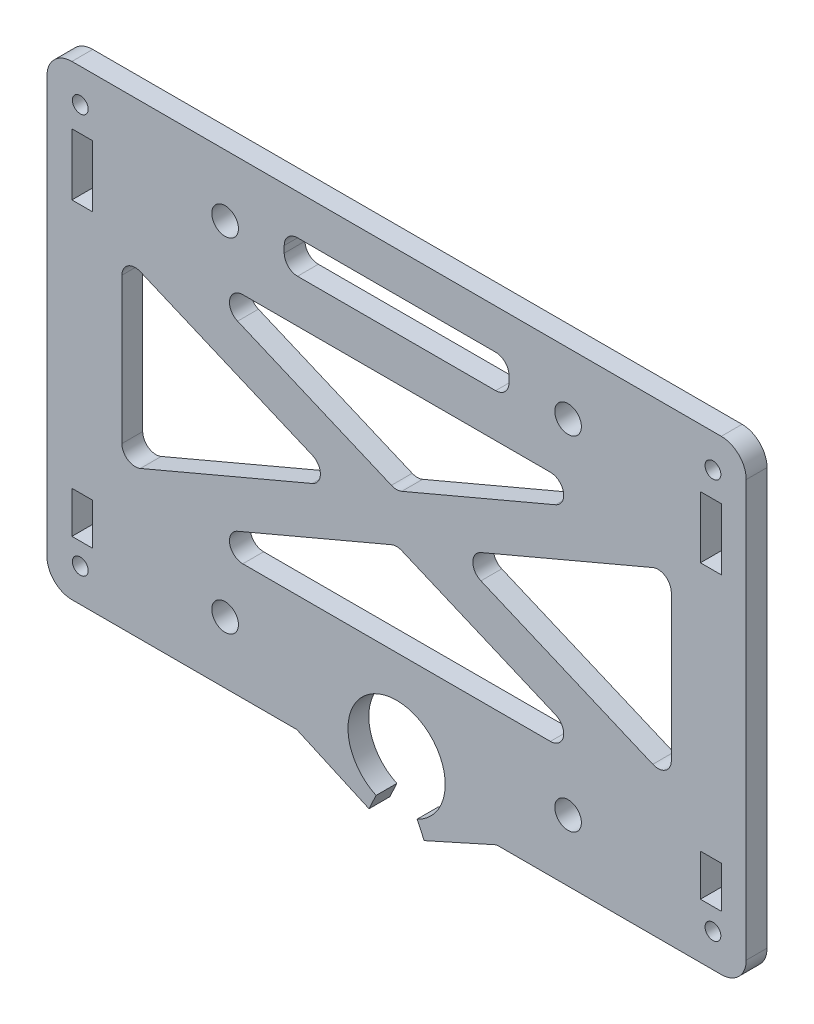
SolidWorks part; units mm, degrees
material "Delrin 2700 NC010, Low Viscosity Acetal Copolymer (SS)"
ref_plane "Front Plane" through (0, 0, 0) normal (0, 0, 1) x (1, 0, 0)
ref_plane "Top Plane" through (0, 0, 0) normal (0, 1, 0) x (1, 0, 0)
ref_plane "Right Plane" through (0, 0, 0) normal (1, 0, 0) x (0, 0, -1)
sketch "Sketch1" plane through (0, 0, 0) normal (0, 0, 1) x (1, 0, 0)
  line L0 (0, -1000) -> (0, 49000) construction
  line L1 (24.765, 17.78) -> (-24.765, 17.78)
  line L2 (26.67, 15.875) -> (26.67, -17.78)
  line L3 (26.67, -17.78) -> (-26.67, -17.78)
  line L4 (-26.67, 15.875) -> (-26.67, -17.78)
  line L5 (26.67, 17.78) -> (-26.67, -17.78) construction
  line L6 (26.67, -17.78) -> (-26.67, 17.78) construction
  line L7 (-1000, 0) -> (49000, 0) construction
  line L8 (-7.62, -17.78) -> (-2.104, -20.26)
  line L15 (-2.104, -20.26) -> (0, -15.748)
  line L16 (7.62, -17.78) -> (2.104, -20.26)
  line L17 (2.104, -20.26) -> (0, -15.748)
  line L18 (0, 0) -> (-24.2469, 20.3456) construction
  circle A0 centre (0, -15.748) radius 3.7084
  circle A1 centre (-24.13, 15.24) radius 0.6032
  circle A2 centre (-13.08, -13.08) radius 1.016
  circle A3 centre (24.13, 15.24) radius 0.6033
  circle A4 centre (-13.08, 13.08) radius 1.016
  circle A5 centre (13.08, 13.08) radius 1.016
  circle A6 centre (13.08, -13.08) radius 1.016
  arc A7 (24.765, -17.78) -> (26.67, -15.875) centre (24.765, -15.875) ccw
  arc A8 (-24.765, -17.78) -> (-26.67, -15.875) centre (-24.765, -15.875) cw
  arc A9 (-24.765, 17.78) -> (-26.67, 15.875) centre (-24.765, 15.875) ccw
  arc A10 (24.765, 17.78) -> (26.67, 15.875) centre (24.765, 15.875) cw
  circle A11 centre (24.13, -15.24) radius 0.6033
  circle A12 centre (-24.13, -15.24) radius 0.6032
  circle A13 centre (0, -15.748) radius 4.9784
  point P0 (0, 0)
  point P9 (0, 0)
  point P11 (0, -7.366)
  point P53 (-13.97, 0)
  dimension "D6" = 7.4168
  dimension "D7" = 1.2065
  dimension "D9" = 2.032
  dimension "D14" = 1.905
  dimension "D15" = 1.905
  dimension "D30" = 2.54
  dimension "D1" = 35.56
  dimension "D4" = 53.34
  dimension "D5" = 15.748
  dimension "D8" = 2.54
  dimension "D10" = 13.08
  dimension "D11" = 13.08
  dimension "D19" = 40
  dimension "D20" = 8.382
  dimension "D21" = 4
  dimension "D23" = 13.97
  dimension "D27" = 7.62
  dimension "D28" = 25
  dimension "D26" = 1.27
extrude "Boss-Extrude1" add sketch "Sketch1" along normal blind 1.5875 contours A10 L1 A9 L4 L3 A0 L2 A6 A5 A4 A1 A2 A3 | L3 A13 L15 A0 | A13 L3 L8 | L3 A13 A0 | L17 A13 L3 A0 | A13 L16 L3 region at (0, 0.4732, 0) region at (5.0756, -18.4873, 0) region at (-5.0756, -18.4873, 0) region at (2.9865, -18.87, 0) region at (3.8235, -17.6582, 0) region at (-2.9865, -18.87, 0)
ref_axis "Axis1" through (0, 0, 0) along (0, 0, 1)
sketch "Sketch2" plane through (0, 0, 1.5875) normal (0, 0, 1) x (1, 0, 0)
  line L0 (0, -1000) -> (0, 49000) construction
  line L1 (-1000, 0) -> (49000, 0) construction
  line L2 (21.0732, -7.1467) -> (-16.7276, 8.89)
  line L3 (20.955, 8.89) -> (-20.955, 8.89)
  line L4 (20.955, 8.89) -> (20.955, -8.89)
  line L5 (20.955, -8.89) -> (-20.955, -8.89)
  line L6 (-20.955, 8.89) -> (-20.955, -8.89)
  line L7 (20.955, 8.89) -> (-20.955, -8.89) construction
  line L8 (20.955, -8.89) -> (-20.955, 8.89) construction
  line L9 (16.7276, 8.89) -> (-20.955, -7.0966)
  line L10 (16.7276, -8.89) -> (-20.955, 7.0966)
  line L11 (20.955, 7.0966) -> (-16.7276, -8.89)
  line L12 (21.5998, 7.3701) -> (-20.3102, -10.4099) construction
  line L13 (20.3102, 10.4099) -> (-21.5998, -7.3701) construction
  line L14 (20.3102, -10.4099) -> (-21.5998, 7.3701) construction
  line L15 (21.5998, -7.3701) -> (-20.3102, 10.4099) construction
  line L16 (24.765, 17.78) -> (-24.765, 17.78) construction
  line L17 (8.5725, 14.732) -> (-8.5725, 14.732)
  line L18 (8.5725, 14.732) -> (8.5725, 12.192)
  line L19 (8.5725, 12.192) -> (-8.5725, 12.192)
  line L20 (-8.5725, 14.732) -> (-8.5725, 12.192)
  line L21 (8.5725, 14.732) -> (-8.5725, 12.192) construction
  line L22 (8.5725, 12.192) -> (-8.5725, 14.732) construction
  point P4 (0, 0)
  point P26 (0, 13.462)
  dimension "D3" = 17.78
  dimension "D4" = 41.91
  dimension "D5" = 3.048
  dimension "D6" = 3.302
  dimension "D7" = 17.145
  dimension "D1" = 1.651
  dimension "D2" = 1.651
extrude "Speed Holes" cut sketch "Sketch2" against normal up to next contours L9 L10 L6 | L9 L3 L2 | L4 L11 L2 | L10 L11 L5 | L17 L20 L19 L18 region at (15.3791, 0, 1.5875) region at (0, 6.5245, 1.5875) region at (0, -6.5245, 1.5875) region at (-15.3791, 0, 1.5875) region at (0, 13.462, 1.5875)
fillet "Fillet1" radius 1.016 16 edges at (-16.7276, -8.89, 0.7937) (-20.955, -7.0966, 0.7937) (0, 1.7934, 0.7937) (16.7276, -8.89, 0.7937) (20.955, -7.0966, 0.7937) (20.955, 7.0966, 0.7937) (-4.2274, 0, 0.7937) (16.7276, 8.89, 0.7937) (4.2274, 0, 0.7937) (-16.7276, 8.89, 0.7937) (0, -1.7934, 0.7937) (-20.955, 7.0966, 0.7937) (-8.5725, 14.732, 0.7937) (-8.5725, 12.192, 0.7937) (8.5725, 14.732, 0.7937) (8.5725, 12.192, 0.7937)
sketch "Sketch5" plane through (0, 0, 1.5875) normal (0, 0, 1) x (1, 0, 0)
  line L0 (24.765, 8.6305) -> (23.1775, 8.6305) construction
  line L1 (24.765, -10.4195) -> (23.1775, -10.4195) construction
  line L2 (24.765, -10.4195) -> (23.1775, -10.4195)
  line L3 (23.1775, -10.4195) -> (23.1775, -13.5945)
  line L4 (24.765, 8.6305) -> (23.1775, 8.6305)
  line L5 (23.1775, -13.5945) -> (24.765, -13.5945)
  line L6 (24.765, -13.5945) -> (24.765, -10.4195)
  line L8 (24.765, 8.6305) -> (24.765, 13.3295)
  line L9 (24.765, 13.3295) -> (23.1775, 13.3295)
  line L10 (23.1775, 13.3295) -> (23.1775, 8.6305)
  dimension "D1" = 4.699
  dimension "D2" = 3.175
extrude "Cut-Extrude1" cut sketch "Sketch5" against normal through all
mirror "Mirror1" about plane through (0, 0, 0) normal (1, 0, 0) of "Cut-Extrude1"
